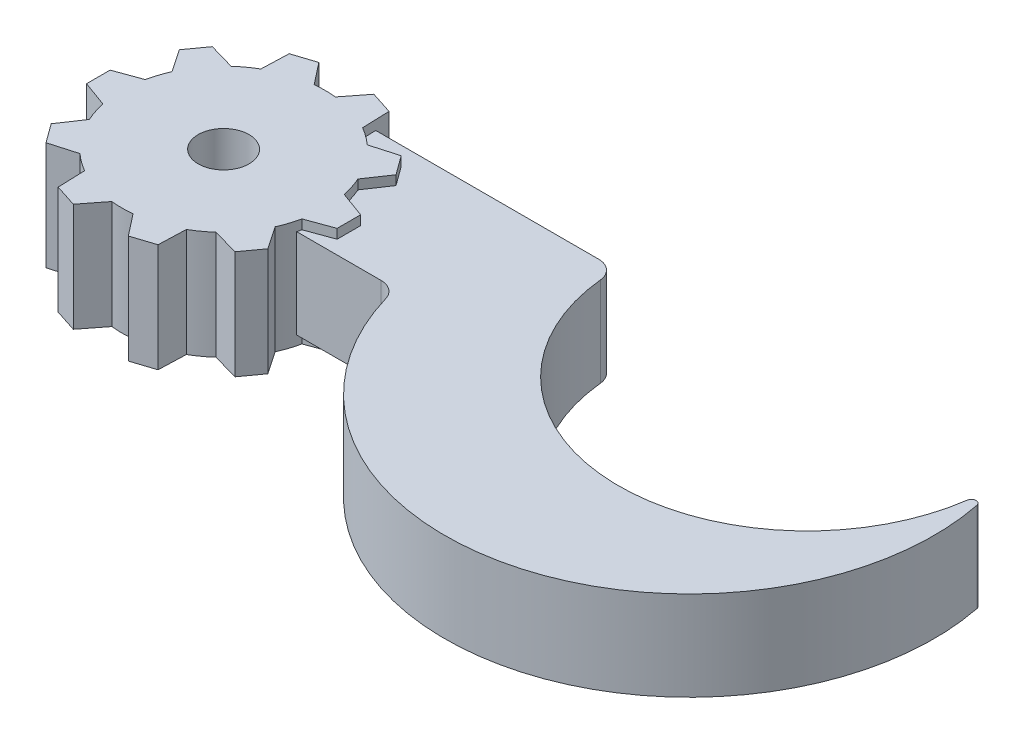
SolidWorks part; units mm, degrees
note: The reader was unsure of these and kept them because the rebuilt part matched: shared geometry of "Croquis1<6>".
ref_plane "Front Plane" through (0, 0, 0) normal (0, 0, 1) x (1, 0, 0)
ref_plane "Top Plane" through (0, 0, 0) normal (0, 1, 0) x (1, 0, 0)
ref_plane "Right Plane" through (0, 0, 0) normal (1, 0, 0) x (0, 0, -1)
sketch "Croquis1" plane through (0, 0, 0) normal (0, 1, 0) x (1, 0, 0)
  line L0 (5.3498, 10.8) -> (0, 10.8) construction
  line L1 (-4.1099, 12.6491) -> (0, 0) construction
  line L2 (5.2987, 12.2628) -> (5.4004, 9.3529)
  line L3 (2.9211, 13.0353) -> (5.2987, 12.2628)
  line L4 (2.9211, 13.0353) -> (1.1285, 10.7409)
  line L5 (11.4947, 6.8063) -> (9.8665, 4.3924)
  line L6 (10.0252, 8.8288) -> (11.4947, 6.8063)
  line L7 (10.0252, 8.8288) -> (7.2263, 8.0262)
  line L8 (13.3, -1.25) -> (10.5639, -2.2459)
  line L9 (13.3, 1.25) -> (13.3, -1.25)
  line L10 (13.3, 1.25) -> (10.5639, 2.2459)
  line L11 (10.0252, -8.8288) -> (7.2263, -8.0262)
  line L12 (11.4947, -6.8063) -> (10.0252, -8.8288)
  line L13 (11.4947, -6.8063) -> (9.8665, -4.3924)
  line L14 (2.9211, -13.0353) -> (1.1285, -10.7409)
  line L15 (5.2987, -12.2628) -> (2.9211, -13.0353)
  line L16 (5.2987, -12.2628) -> (5.4004, -9.3529)
  line L17 (-5.2987, -12.2628) -> (-5.4004, -9.3529)
  line L18 (-2.9211, -13.0353) -> (-5.2987, -12.2628)
  line L19 (-2.9211, -13.0353) -> (-1.1285, -10.7409)
  line L20 (-11.4947, -6.8063) -> (-9.8665, -4.3924)
  line L21 (-10.0252, -8.8288) -> (-11.4947, -6.8063)
  line L22 (-5.2987, 12.2628) -> (-2.9211, 13.0353)
  line L23 (-5.2987, 12.2628) -> (-5.4004, 9.3529)
  line L24 (-2.9211, 13.0353) -> (-1.1285, 10.7409)
  line L25 (-10.0252, -8.8288) -> (-7.2263, -8.0262)
  line L26 (-13.3, 1.25) -> (-10.5639, 2.2459)
  line L27 (-13.3, -1.25) -> (-13.3, 1.25)
  line L28 (-13.3, -1.25) -> (-10.5639, -2.2459)
  line L29 (-10.0252, 8.8288) -> (-7.2263, 8.0262)
  line L30 (-11.4947, 6.8063) -> (-10.0252, 8.8288)
  line L31 (0, -2.7) -> (10.4571, -2.7) construction
  line L32 (5.3498, 10.8) -> (29.0254, 10.8)
  line L33 (10.4571, -2.7) -> (19.4273, -2.7)
  line L34 (0, 0) -> (72.0237, 0) construction
  line L41 (-11.4947, 6.8063) -> (-9.8665, 4.3924)
  circle A0 centre (0, 0) radius 10.8
  arc A2 (71.7242, 8.2454) -> (70.7387, 8.2183) centre (71.2337, 8.148) ccw
  arc A3 (70.7387, 8.2183) -> (31.0151, 9.0026) centre (50.9247, 11.0295) cw
  arc A4 (71.7242, 8.2454) -> (21.346, -4.1356) centre (46.2557, 3.1919) cw
  arc A5 (21.346, -4.1356) -> (19.4273, -2.7) centre (19.4273, -4.7) ccw
  arc A6 (31.0151, 9.0026) -> (29.0254, 10.8) centre (29.0254, 8.8) ccw
  circle A7 centre (0, 0) radius 2.7
  point P48 (0.0588, 0.1537)
  point P49 (0, 0)
  point P66 (0, 0)
  dimension "D5" = 2
  dimension "D3" = 0.5
  dimension "D7" = 20.0124
  dimension "D8" = 25.965
  dimension "D11" = 21.6
  dimension "D9" = 5.4
  dimension "D13" = 11.0295
  dimension "D2" = 13.3
  dimension "D4" = 2.9117
  dimension "D6" = 46.2557
  dimension "D10" = 29.0254
  dimension "D12" = 8.9703
  dimension "D14" = 40
  dimension "D15" = 2.9117
  dimension "D16" = 2.3776
  dimension "D17" = 10
extrude "Saliente-Extruir1" add sketch "Croquis1" along normal blind 11.5 contours A0 A7 | A0 L8 L9 L10 | A0 L5 L6 L7 | A0 L2 L3 L4 | A0 L24 L22 L23 | A0 L29 L30 L41 | A0 L26 L27 L28 | A0 L20 L21 L25 | A0 L17 L18 L19 | A0 L14 L15 L16 | A0 L11 L12 L13
extrude "Boss-Extrude1" add sketch "Croquis1<6>" along normal blind 9.5 from offset 1
sketch "Croquis1<6>" plane through (0, 0, 0) normal (0, 1, 0) x (1, 0, 0) same geometry as "Croquis1"
sketch "Sketch2" plane through (0, 0, 0) normal (1, 0, 0) x (0, 0, -1)
  line L0 (0, -5.9252) -> (0, 14.6503) construction
